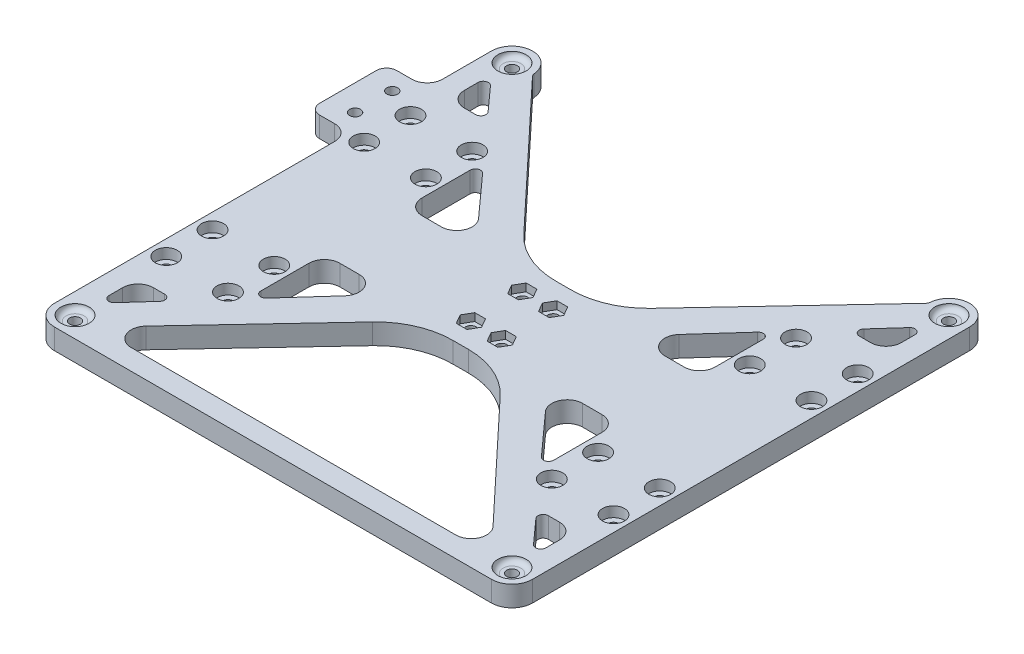
SolidWorks part; units mm, degrees
ref_plane "Front Plane" through (0, 0, 0) normal (0, 0, 1) x (1, 0, 0)
ref_plane "Top Plane" through (0, 0, 0) normal (0, 1, 0) x (1, 0, 0)
ref_plane "Right Plane" through (0, 0, 0) normal (1, 0, 0) x (0, 0, -1)
sketch "Sketch1" plane through (0, 0, 0) normal (0, 1, 0) x (1, 0, 0)
  line L0 (0, 162) -> (55, 101)
  line L1 (0, 0) -> (170, 0) construction
  line L2 (0, 0) -> (0, 170) construction
  line L3 (0, 170) -> (170, 170) construction
  line L4 (170, 0) -> (170, 170) construction
  line L5 (55, 69) -> (0, 8)
  line L6 (8, 0) -> (69, 65)
  line L7 (101, 65) -> (162, 0)
  line L8 (170, 8) -> (115, 69)
  line L9 (115, 101) -> (170, 162)
  line L10 (8, 170) -> (69, 105)
  line L11 (101, 105) -> (162, 170)
  line L12 (55, 105) -> (115, 105) construction
  line L13 (69, 105) -> (101, 105)
  line L15 (69, 65) -> (101, 65)
  line L16 (115, 101) -> (115, 69)
  line L17 (55, 105) -> (115, 65) construction
  line L18 (55, 65) -> (115, 105) construction
  line L19 (115, 105) -> (115, 65) construction
  line L20 (115, 65) -> (55, 65) construction
  line L21 (55, 65) -> (55, 105) construction
  line L22 (55, 85) -> (115, 85) construction
  line L23 (85, 105) -> (85, 65) construction
  line L24 (55, 101) -> (0, 101)
  line L29 (-8, 170) -> (-8, 145)
  line L30 (0, 162) -> (0, 101)
  line L31 (8, 0) -> (162, 0)
  line L32 (0, -8) -> (170, -8)
  line L33 (178, 170) -> (178, 0)
  line L34 (170, 162) -> (170, 8)
  line L35 (-8, 115) -> (-8, 0)
  line L37 (0, 69) -> (55, 69)
  line L38 (0, 69) -> (0, 8)
  line L39 (-8, 115) -> (-23.806, 115)
  line L40 (-23.806, 145) -> (-8, 145)
  line L41 (-23.806, 115) -> (-23.806, 145)
  circle A0 centre (0, 170) radius 2.1
  circle A1 centre (170, 170) radius 2.1
  circle A2 centre (170, 0) radius 2.1
  circle A3 centre (0, 0) radius 2.1
  arc A6 (170, -8) -> (178, 0) centre (170, 0) ccw
  arc A7 (-8, 0) -> (0, -8) centre (0, 0) ccw
  arc A8 (8, 170) -> (-8, 170) centre (0, 170) ccw
  arc A9 (178, 170) -> (162, 170) centre (170, 170) ccw
  point P9 (85, -8)
  point P12 (-23.806, 130)
  point P16 (85, 105)
  point P42 (85, 85)
  point P43 (85, 170)
  point P55 (178, 85)
  dimension "D2" = 4.2
  dimension "D3" = 40
  dimension "D4" = 30
  dimension "D1" = 170
  dimension "D5" = 60
  dimension "D6" = 40
  dimension "D7" = 32
  dimension "D8" = 32
  dimension "D9" = 170
extrude "Boss-Extrude1" add sketch "Sketch1" along normal blind 8
fillet "Fillet2" radius 4 2 edges at (-23.806, 4, -145) (-23.806, 4, -115) tangent propagation no
sketch "Sketch2" plane through (0, 8, 0) normal (0, 1, 0) x (1, 0, 0)
  line L1 (79, 95) -> (91, 95) construction
  line L2 (79, 95) -> (79, 75) construction
  line L3 (79, 75) -> (91, 75) construction
  line L4 (91, 95) -> (91, 75) construction
  line L5 (79, 95) -> (91, 75) construction
  line L6 (79, 75) -> (91, 95) construction
  line L7 (178, 0) -> (178, 170) construction
  line L8 (0, -8) -> (170, -8) construction
  circle A0 centre (79, 95) radius 2.1
  circle A1 centre (91, 95) radius 2.1
  circle A2 centre (91, 75) radius 2.1
  circle A3 centre (79, 75) radius 2.1
  point P0 (85, 85)
  point P11 (178, 85)
  point P19 (85, -8)
  dimension "D3" = 4.2
  dimension "D1" = 20
  dimension "D2" = 12
extrude "Cut-Extrude1" cut sketch "Sketch2" against normal blind 10
sketch "Sketch3" plane through (0, 8, 0) normal (0, 1, 0) x (1, 0, 0)
  line L1 (81.0785, 91.4) -> (83.1569, 95)
  line L2 (83.1569, 95) -> (81.0785, 98.6)
  line L3 (81.0785, 98.6) -> (76.9215, 98.6)
  line L4 (76.9215, 98.6) -> (74.8431, 95)
  line L5 (74.8431, 95) -> (76.9215, 91.4)
  line L6 (76.9215, 91.4) -> (81.0785, 91.4)
  line L7 (93.0785, 91.4) -> (95.1569, 95)
  line L8 (95.1569, 95) -> (93.0785, 98.6)
  line L9 (93.0785, 98.6) -> (88.9215, 98.6)
  line L10 (88.9215, 98.6) -> (86.8431, 95)
  line L11 (86.8431, 95) -> (88.9215, 91.4)
  line L12 (88.9215, 91.4) -> (93.0785, 91.4)
  line L13 (93.0785, 71.4) -> (95.1569, 75)
  line L14 (95.1569, 75) -> (93.0785, 78.6)
  line L15 (93.0785, 78.6) -> (88.9215, 78.6)
  line L16 (88.9215, 78.6) -> (86.8431, 75)
  line L17 (86.8431, 75) -> (88.9215, 71.4)
  line L18 (88.9215, 71.4) -> (93.0785, 71.4)
  line L19 (76.9215, 71.4) -> (81.0785, 71.4)
  line L20 (81.0785, 71.4) -> (83.1569, 75)
  line L21 (83.1569, 75) -> (81.0785, 78.6)
  line L22 (81.0785, 78.6) -> (76.9215, 78.6)
  line L23 (76.9215, 78.6) -> (74.8431, 75)
  line L24 (74.8431, 75) -> (76.9215, 71.4)
  circle A0 centre (79, 95) radius 3.6 construction
  circle A1 centre (91, 95) radius 3.6 construction
  circle A2 centre (91, 75) radius 3.6 construction
  circle A3 centre (79, 75) radius 3.6 construction
  dimension "D1" = 7.2
extrude "Cut-Extrude2" cut sketch "Sketch3" against normal blind 3
sketch "Sketch4" plane through (0, 8, 0) normal (0, 1, 0) x (1, 0, 0)
  line L0 (-13.806, 137.25) -> (-13.806, 122.75) construction
  line L2 (-23.806, 141) -> (-23.806, 119) construction
  circle A0 centre (-13.806, 137.25) radius 2.125
  circle A1 centre (-13.806, 122.75) radius 2.125
  point P2 (-13.806, 130)
  point P10 (-23.806, 130)
  dimension "D2" = 4.25
  dimension "D1" = 14.5
  dimension "D3" = 10
extrude "Cut-Extrude3" cut sketch "Sketch4" against normal blind 10
sketch "Sketch5" plane through (0, 0, 0) normal (0, -1, 0) x (1, 0, 0)
  line L1 (-15.8845, -133.65) -> (-17.9629, -137.25)
  line L2 (-17.9629, -137.25) -> (-15.8845, -140.85)
  line L3 (-15.8845, -140.85) -> (-11.7275, -140.85)
  line L4 (-11.7275, -140.85) -> (-9.6491, -137.25)
  line L5 (-9.6491, -137.25) -> (-11.7275, -133.65)
  line L6 (-11.7275, -133.65) -> (-15.8845, -133.65)
  line L7 (-15.8845, -119.15) -> (-17.9629, -122.75)
  line L8 (-17.9629, -122.75) -> (-15.8845, -126.35)
  line L9 (-15.8845, -126.35) -> (-11.7275, -126.35)
  line L10 (-11.7275, -126.35) -> (-9.6491, -122.75)
  line L11 (-9.6491, -122.75) -> (-11.7275, -119.15)
  line L12 (-11.7275, -119.15) -> (-15.8845, -119.15)
  circle A0 centre (-13.806, -137.25) radius 3.6 construction
  circle A1 centre (-13.806, -122.75) radius 3.6 construction
  dimension "D1" = 7.2
extrude "Cut-Extrude4" cut sketch "Sketch5" against normal blind 3
sketch "Sketch6" plane through (0, 8, 0) normal (0, 1, 0) x (1, 0, 0)
  line L0 (178, 0) -> (178, 170) construction
  line L1 (10, 123.5) -> (160, 123.5) construction
  line L2 (10, 123.5) -> (10, 46.5) construction
  line L3 (10, 46.5) -> (160, 46.5) construction
  line L4 (160, 123.5) -> (160, 46.5) construction
  line L5 (10, 123.5) -> (160, 46.5) construction
  line L6 (10, 46.5) -> (160, 123.5) construction
  line L8 (115, 101) -> (115, 69) construction
  line L9 (28, 139.5) -> (-8, 139.5)
  line L10 (28, 139.5) -> (28, 107.5)
  line L11 (28, 107.5) -> (-8, 107.5)
  line L12 (-8, 139.5) -> (-8, 107.5)
  line L13 (28, 139.5) -> (-8, 107.5) construction
  line L14 (28, 107.5) -> (-8, 139.5) construction
  line L15 (142, 139.5) -> (178, 139.5)
  line L16 (142, 139.5) -> (142, 107.5)
  line L17 (142, 107.5) -> (178, 107.5)
  line L18 (178, 139.5) -> (178, 107.5)
  line L19 (142, 139.5) -> (178, 107.5) construction
  line L20 (142, 107.5) -> (178, 139.5) construction
  line L21 (142, 62.5) -> (178, 62.5)
  line L22 (142, 62.5) -> (142, 30.5)
  line L23 (142, 30.5) -> (178, 30.5)
  line L24 (178, 62.5) -> (178, 30.5)
  line L25 (142, 62.5) -> (178, 30.5) construction
  line L26 (142, 30.5) -> (178, 62.5) construction
  line L27 (28, 62.5) -> (-8, 62.5)
  line L28 (28, 62.5) -> (28, 30.5)
  line L29 (28, 30.5) -> (-8, 30.5)
  line L30 (-8, 62.5) -> (-8, 30.5)
  line L31 (28, 62.5) -> (-8, 30.5) construction
  line L32 (28, 30.5) -> (-8, 62.5) construction
  line L33 (170, 101) -> (115, 101)
  line L34 (170, 101) -> (170, 69)
  line L35 (170, 69) -> (115, 69)
  line L36 (115, 101) -> (115, 69)
  line L37 (0, 101) -> (55, 101) construction
  line L38 (55, 69) -> (0, 69) construction
  line L39 (170, 8) -> (170, 162) construction
  line L40 (0, -8) -> (170, -8) construction
  point P0 (85, 85)
  point P10 (178, 85)
  point P43 (85, -8)
  dimension "D1" = 150
  dimension "D2" = 36
  dimension "D3" = 32
  dimension "D4" = 77
extrude "Boss-Extrude2" add sketch "Sketch6" against normal up to surface (8 mm away) up to face at (-13.806, 0, -137.25)
sketch "Sketch7" plane through (0, 8, 0) normal (0, 1, 0) x (1, 0, 0)
  line L1 (-2, 132.5) -> (22, 132.5) construction
  line L2 (-2, 132.5) -> (-2, 114.5) construction
  line L3 (-2, 114.5) -> (22, 114.5) construction
  line L4 (22, 132.5) -> (22, 114.5) construction
  line L5 (-2, 132.5) -> (22, 114.5) construction
  line L6 (-2, 114.5) -> (22, 132.5) construction
  line L7 (-2, 55.5) -> (22, 55.5) construction
  line L8 (-2, 55.5) -> (-2, 37.5) construction
  line L9 (-2, 37.5) -> (22, 37.5) construction
  line L10 (22, 55.5) -> (22, 37.5) construction
  line L11 (-2, 55.5) -> (22, 37.5) construction
  line L12 (-2, 37.5) -> (22, 55.5) construction
  line L13 (148, 55.5) -> (172, 55.5) construction
  line L14 (148, 55.5) -> (148, 37.5) construction
  line L15 (148, 37.5) -> (172, 37.5) construction
  line L16 (172, 55.5) -> (172, 37.5) construction
  line L17 (148, 55.5) -> (172, 37.5) construction
  line L18 (148, 37.5) -> (172, 55.5) construction
  line L19 (148, 132.5) -> (172, 132.5) construction
  line L20 (148, 132.5) -> (148, 114.5) construction
  line L21 (148, 114.5) -> (172, 114.5) construction
  line L22 (172, 132.5) -> (172, 114.5) construction
  line L23 (148, 132.5) -> (172, 114.5) construction
  line L24 (148, 114.5) -> (172, 132.5) construction
  line L27 (-8, 170) -> (-8, 145) construction
  line L28 (178, 0) -> (178, 170) construction
  line L29 (0, 107.5) -> (28, 107.5) construction
  line L30 (0, 30.5) -> (20.2869, 30.5) construction
  circle A0 centre (-2, 132.5) radius 2.1
  circle A1 centre (22, 132.5) radius 2.1
  circle A2 centre (22, 114.5) radius 2.1
  circle A3 centre (-2, 114.5) radius 2.1
  circle A4 centre (-2, 55.5) radius 2.1
  circle A5 centre (22, 55.5) radius 2.1
  circle A6 centre (-2, 37.5) radius 2.1
  circle A7 centre (22, 37.5) radius 2.1
  circle A8 centre (148, 37.5) radius 2.1
  circle A9 centre (172, 37.5) radius 2.1
  circle A10 centre (172, 55.5) radius 2.1
  circle A11 centre (148, 55.5) radius 2.1
  circle A12 centre (148, 114.5) radius 2.1
  circle A13 centre (172, 114.5) radius 2.1
  circle A14 centre (172, 132.5) radius 2.1
  circle A15 centre (148, 132.5) radius 2.1
  point P0 (10, 123.5)
  point P5 (10, 46.5)
  point P10 (160, 46.5)
  point P15 (160, 123.5)
  dimension "D5" = 4.2
  dimension "D1" = 24
  dimension "D2" = 18
  dimension "D3" = 18
  dimension "D4" = 18
  dimension "D6" = 16
  dimension "D7" = 16
extrude "Cut-Extrude5" cut sketch "Sketch7" against normal blind 10
sketch "Sketch8" plane through (0, 8, 0) normal (0, 1, 0) x (1, 0, 0)
  line L1 (28, 107.5) -> (0, 107.5)
  line L2 (28, 107.5) -> (28, 101)
  line L3 (28, 101) -> (0, 101)
  line L4 (0, 107.5) -> (0, 101)
  line L5 (28, 62.5) -> (0, 62.5)
  line L6 (28, 62.5) -> (28, 69)
  line L7 (28, 69) -> (0, 69)
  line L8 (0, 62.5) -> (0, 69)
  line L9 (142, 62.5) -> (170, 62.5)
  line L10 (142, 62.5) -> (142, 69)
  line L11 (142, 69) -> (170, 69)
  line L12 (170, 62.5) -> (170, 69)
  line L13 (142, 107.5) -> (170, 107.5)
  line L14 (142, 107.5) -> (142, 101)
  line L15 (142, 101) -> (170, 101)
  line L16 (170, 107.5) -> (170, 101)
  line L17 (0, 30.5) -> (23, 30.5)
  line L18 (0, 30.5) -> (0, 24.5)
  line L19 (0, 24.5) -> (23, 24.5)
  line L20 (23, 30.5) -> (23, 24.5)
  line L21 (170, 30.5) -> (147, 30.5)
  line L22 (170, 30.5) -> (170, 24.5)
  line L23 (170, 24.5) -> (147, 24.5)
  line L24 (147, 30.5) -> (147, 24.5)
  line L25 (0, 139.5) -> (23, 139.5)
  line L26 (0, 139.5) -> (0, 145.5)
  line L27 (0, 145.5) -> (23, 145.5)
  line L28 (23, 139.5) -> (23, 145.5)
  line L29 (170, 139.5) -> (147, 139.5)
  line L30 (170, 139.5) -> (170, 145.5)
  line L31 (170, 145.5) -> (147, 145.5)
  line L32 (147, 139.5) -> (147, 145.5)
  dimension "D1" = 23
  dimension "D2" = 6
extrude "Boss-Extrude3" add sketch "Sketch8" against normal up to surface (8 mm away) up to face at (22, 0, -53.4)
fillet "Fillet3" radius 6 16 edges at (170, 4, -24.5) (170, 4, -145.5) (0, 4, -145.5) (0, 4, -24.5) (115, 4, -101) (115, 4, -69) (55, 4, -101) (55, 4, -69) (28, 4, -101) (28, 4, -69) (142, 4, -69) (142, 4, -101) (8, 4, 0) (162, 4, 0) (-8, 4, -145) (-8, 4, -115)
fillet "Fillet4" radius 2 14 edges at (14.877, 4, -145.5) (0, 4, -162) (14.877, 4, -24.5) (0, 4, -8) (155.123, 4, -24.5) (170, 4, -8) (170, 4, -162) (155.123, 4, -145.5) (28, 4, -39.0545) (142, 4, -39.0545) (142, 4, -130.9455) (28, 4, -130.9455) (162, 4, -170) (8, 4, -170)
fillet "Fillet5" radius 30 4 edges at (69, 4, -65) (101, 4, -65) (101, 4, -105) (69, 4, -105)
sketch "Sketch9" plane through (0, 8, 0) normal (0, 1, 0) x (1, 0, 0)
  circle A0 centre (22, 132.5) radius 4.25
  circle A1 centre (22, 114.5) radius 4.25
  circle A2 centre (-2, 114.5) radius 4.25
  circle A3 centre (-2, 132.5) radius 4.25
  circle A4 centre (-2, 55.5) radius 4.25
  circle A5 centre (22, 55.5) radius 4.25
  circle A6 centre (22, 37.5) radius 4.25
  circle A7 centre (-2, 37.5) radius 4.25
  circle A8 centre (148, 37.5) radius 4.25
  circle A9 centre (148, 55.5) radius 4.25
  circle A10 centre (172, 55.5) radius 4.25
  circle A11 centre (172, 37.5) radius 4.25
  circle A12 centre (172, 114.5) radius 4.25
  circle A13 centre (172, 132.5) radius 4.25
  circle A14 centre (148, 132.5) radius 4.25
  circle A15 centre (148, 114.5) radius 4.25
  dimension "D1" = 8.5
extrude "Cut-Extrude6" cut sketch "Sketch9" against normal blind 4
sketch "Sketch10" plane through (0, 8, 0) normal (0, 1, 0) x (1, 0, 0)
  circle A0 centre (0, 0) radius 5.5
  circle A1 centre (0, 0) radius 2.1 construction
  circle A2 centre (0, 170) radius 5.5
  circle A3 centre (170, 170) radius 5.5
  circle A4 centre (170, 0) radius 5.5
  circle A5 centre (0, 170) radius 2.1 construction
  circle A6 centre (170, 0) radius 2.1 construction
  circle A7 centre (170, 170) radius 2.1 construction
  dimension "D1" = 11
extrude "Cut-Extrude7" cut sketch "Sketch10" against normal blind 2
fillet "Fillet6" radius 2 4 edges at (170, 6, 5.5) (170, 6, -164.5) (0, 6, 5.5) (0, 6, -164.5)
